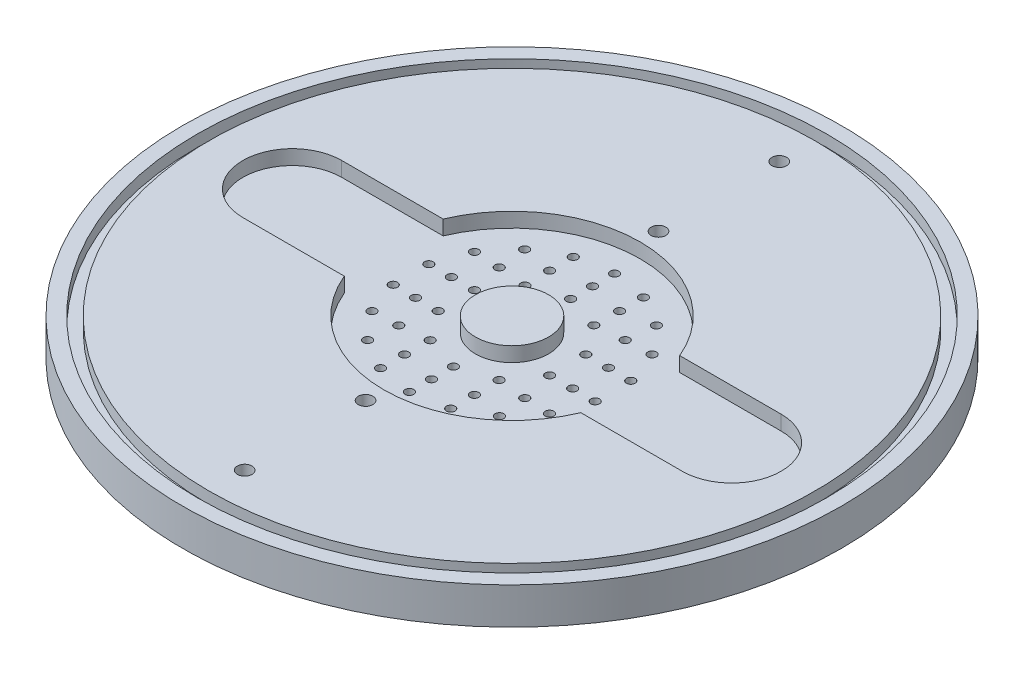
SolidWorks part; units mm, degrees
material "AISI 304"
ref_plane "Front Plane" through (0, 0, 0) normal (0, 0, 1) x (1, 0, 0)
ref_plane "Top Plane" through (0, 0, 0) normal (0, 1, 0) x (1, 0, 0)
ref_plane "Right Plane" through (0, 0, 0) normal (1, 0, 0) x (0, 0, -1)
sketch "Main Shape Profile" plane through (0, 0, 0) normal (0, 0, 1) x (1, 0, 0)
  line L1 (57.15, 0) -> (57.15, 6.35)
  line L2 (57.15, 6.35) -> (0, 6.35)
  line L5 (0, 6.35) -> (0, 0)
  line L6 (0, 0) -> (57.15, 0)
  line L7 (0, 0) -> (0, -50000) construction
  point P4 (0, 0)
  dimension "Kerosene Plate Outer Diameter" = 114.3
  dimension "Kerosene Plate Thickness" = 6.35
revolve "Main Shape" add sketch "Main Shape Profile" angle 360 about L7
sketch "O Rings Profile" plane through (0, 0, 0) normal (0, 0, 1) x (1, 0, 0)
  line L0 (57.15, 6.35) -> (-57.15, 6.35) construction
  line L1 (52.578, 6.35) -> (54.61, 6.35)
  line L2 (52.578, 6.35) -> (52.578, 4.318)
  line L3 (52.578, 4.318) -> (54.61, 4.318)
  line L4 (54.61, 6.35) -> (54.61, 4.318)
  line L5 (-57.15, 0) -> (57.15, 0) construction
  line L6 (52.578, 0) -> (54.61, 0)
  line L7 (52.578, 0) -> (52.578, 2.032)
  line L8 (52.578, 2.032) -> (54.61, 2.032)
  line L9 (54.61, 0) -> (54.61, 2.032)
  line L10 (57.15, 0) -> (57.15, 6.35) construction
  line L11 (0, 0) -> (0, -50000) construction
  dimension "O Ring Depth1" = 2.032
  dimension "O Ring Width" = 2.032
  dimension "O Ring Position" = 2.54
revolve "O-Rings Cutout" cut sketch "O Rings Profile" angle 360 about L11
sketch "Injector Well Profile" plane through (0, 6.35, 0) normal (0, 1, 0) x (1, 0, 0)
  line L0 (-38.1, 0) -> (38.1, 0) construction
  line L1 (-38.1, 8.575) -> (-20.5041, 8.575)
  line L2 (-38.1, -8.575) -> (-20.5041, -8.575)
  line L3 (20.5041, 8.575) -> (38.1, 8.575)
  line L4 (20.5041, -8.575) -> (38.1, -8.575)
  arc A0 (-20.5041, -8.575) -> (20.5041, -8.575) centre (0, 0) ccw
  circle A1 centre (0, 0) radius 6.35
  arc A2 (-38.1, 8.575) -> (-38.1, -8.575) centre (-38.1, 0) ccw
  arc A3 (38.1, -8.575) -> (38.1, 8.575) centre (38.1, 0) ccw
  arc A4 (20.5041, 8.575) -> (-20.5041, 8.575) centre (0, 0) ccw
  point P6 (0, 0)
  dimension "Kerosene Mainfold Diameter" = 44.45
  dimension "Slot Radius" = 17.1501
  dimension "Standoff Diameter" = 12.7
  dimension "Slot Diameter" = 76.2
extrude "Injector Well" cut sketch "Injector Well Profile" against normal blind 2.54
sketch "Dowel Holes Profile" plane through (0, 6.35, 0) normal (0, 1, 0) x (1, 0, 0)
  line L0 (0, -46.355) -> (0, -25.4) construction
  line L1 (0, -25.4) -> (0, -22.225) construction
  line L2 (0, 25.4) -> (0, 22.225) construction
  line L3 (0, 25.4) -> (0, 46.355) construction
  line L4 (0, 46.355) -> (0, 52.578) construction
  line L5 (0, -46.355) -> (0, -52.578) construction
  circle A1 centre (0, 25.4) radius 1.27
  circle A2 centre (0, 46.355) radius 1.27
  circle A3 centre (0, -46.355) radius 1.27
  circle A4 centre (0, -25.4) radius 1.27
  arc A5 (-20.5041, -8.575) -> (20.5041, -8.575) centre (0, 0) ccw construction
  arc A6 (20.5041, 8.575) -> (-20.5041, 8.575) centre (0, 0) ccw construction
  circle A7 centre (0, 0) radius 52.578 construction
  circle A8 centre (0, 0) radius 52.578 construction
  dimension "Dowel Hole Diameter" = 2.54
  dimension "Dowel Placement Inner Diameter" = 50.8
  dimension "Dowel Placement Outer Diameter" = 92.71
extrude "Dowel Holes" cut sketch "Dowel Holes Profile" against normal blind 2.54
sketch "Injector Holes" plane through (0, 3.81, 0) normal (0, 1, 0) x (1, 0, 0)
  line L0 (0, -10.16) -> (0, -13.97) construction
  line L1 (0, -13.97) -> (0, -17.78) construction
  circle A0 centre (0, 0) radius 10.16 construction
  circle A1 centre (0, 0) radius 13.97 construction
  circle A2 centre (0, 0) radius 17.78 construction
  circle A4 centre (0, -17.78) radius 0.7493
  circle A5 centre (0, -13.97) radius 0.7493
  circle A6 centre (0, -10.16) radius 0.7493
  circle A7 centre (-6.0811, -16.7077) radius 0.7493
  circle A11 centre (-11.4288, -13.6203) radius 0.7493
  circle A12 centre (-15.3979, -8.89) radius 0.7493
  circle A13 centre (-17.5099, -3.0875) radius 0.7493
  circle A22 centre (-17.5099, 3.0875) radius 0.7493
  circle A23 centre (-15.3979, 8.89) radius 0.7493
  circle A24 centre (-11.4288, 13.6203) radius 0.7493
  circle A25 centre (-6.0811, 16.7077) radius 0.7493
  circle A26 centre (0, 17.78) radius 0.7493
  circle A27 centre (6.0811, 16.7077) radius 0.7493
  circle A28 centre (11.4288, 13.6203) radius 0.7493
  circle A29 centre (15.3979, 8.89) radius 0.7493
  circle A30 centre (17.5099, 3.0875) radius 0.7493
  circle A31 centre (17.5099, -3.0875) radius 0.7493
  circle A32 centre (15.3979, -8.89) radius 0.7493
  circle A33 centre (11.4288, -13.6203) radius 0.7493
  circle A35 centre (-6.0614, -12.5865) radius 0.7493
  circle A36 centre (-10.9222, -8.7102) radius 0.7493
  circle A37 centre (-13.6197, -3.1086) radius 0.7493
  circle A38 centre (-13.6197, 3.1086) radius 0.7493
  circle A39 centre (-10.9222, 8.7102) radius 0.7493
  circle A40 centre (-6.0614, 12.5865) radius 0.7493
  circle A41 centre (0, 13.97) radius 0.7493
  circle A42 centre (6.0614, 12.5865) radius 0.7493
  circle A43 centre (10.9222, 8.7102) radius 0.7493
  circle A44 centre (13.6197, 3.1086) radius 0.7493
  circle A45 centre (13.6197, -3.1086) radius 0.7493
  circle A46 centre (10.9222, -8.7102) radius 0.7493
  circle A48 centre (-5.9719, -8.2196) radius 0.7493
  circle A49 centre (-9.6627, -3.1396) radius 0.7493
  circle A50 centre (-9.6627, 3.1396) radius 0.7493
  circle A51 centre (-5.9719, 8.2196) radius 0.7493
  circle A52 centre (0, 10.16) radius 0.7493
  circle A53 centre (5.9719, 8.2196) radius 0.7493
  circle A54 centre (9.6627, 3.1396) radius 0.7493
  circle A55 centre (9.6627, -3.1396) radius 0.7493
  circle A56 centre (5.9719, -8.2196) radius 0.7493
  circle A59 centre (6.0614, -12.5865) radius 0.7493
  circle A60 centre (6.0811, -16.7077) radius 0.7493
  point P66 (0, 0)
  point P94 (0, 0)
  point P114 (0, 0)
  dimension "Injector Hole Diameter" = 1.4986
  dimension "Inner Ring Diameter" = 20.32
  dimension "Outer Ring Diameter" = 35.56
  dimension "Outer Ring Holes Num" = 18
  dimension "Middle Ring Holes Num" = 14
  dimension "Inner Ring Holes Num" = 10
extrude "Circular Injector Holes" cut sketch "Injector Holes" against normal through all
